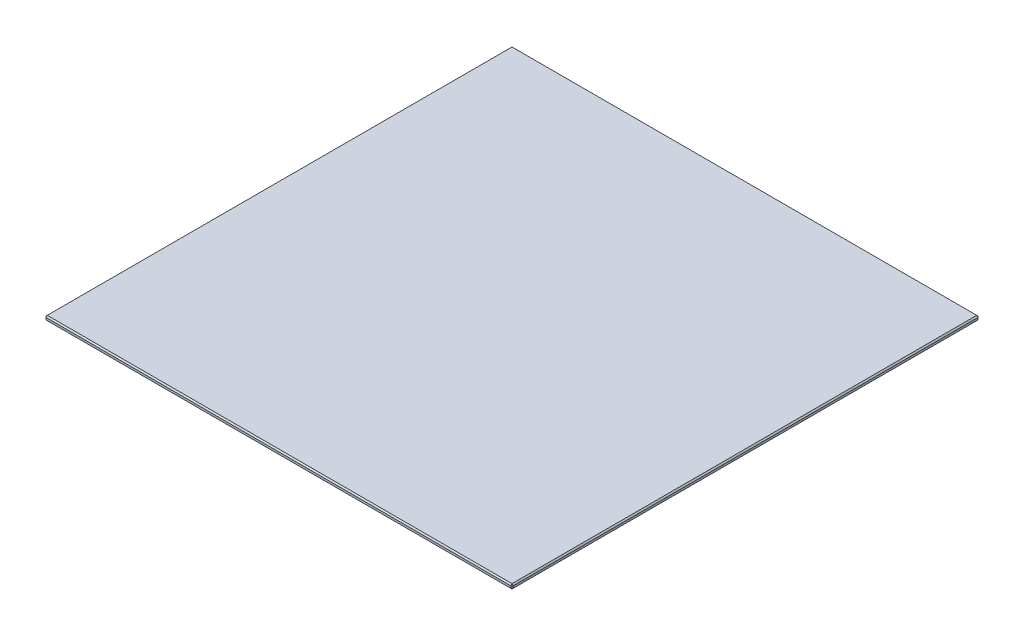
SolidWorks part; units mm, degrees
ref_plane "Front Plane" through (0, 0, 0) normal (0, 0, 1) x (1, 0, 0)
ref_plane "Top Plane" through (0, 0, 0) normal (0, 1, 0) x (1, 0, 0)
ref_plane "Right Plane" through (0, 0, 0) normal (1, 0, 0) x (0, 0, -1)
sketch "Sketch1" plane through (0, 0, 0) normal (0, 1, 0) x (1, 0, 0)
  line L1 (-150, 150) -> (150, 150)
  line L2 (-150, 150) -> (-150, -150)
  line L3 (-150, -150) -> (150, -150)
  line L4 (150, 150) -> (150, -150)
  dimension "D1" = 300
  dimension "D2" = 150
  dimension "D3" = 300
  dimension "D4" = 150
extrude "Boss-Extrude1" add sketch "Sketch1" along normal blind 3
chamfer "Chamfer1" distance 0.8 angle 45 12 edges at (150, 1.5, 150) (150, 0, 0) (150, 3, 0) (150, 1.5, -150) (0, 0, -150) (0, 3, -150) (-150, 1.5, -150) (-150, 0, 0) (0, 0, 150) (-150, 1.5, 150) (-150, 3, 0) (0, 3, 150) tangent propagation no
